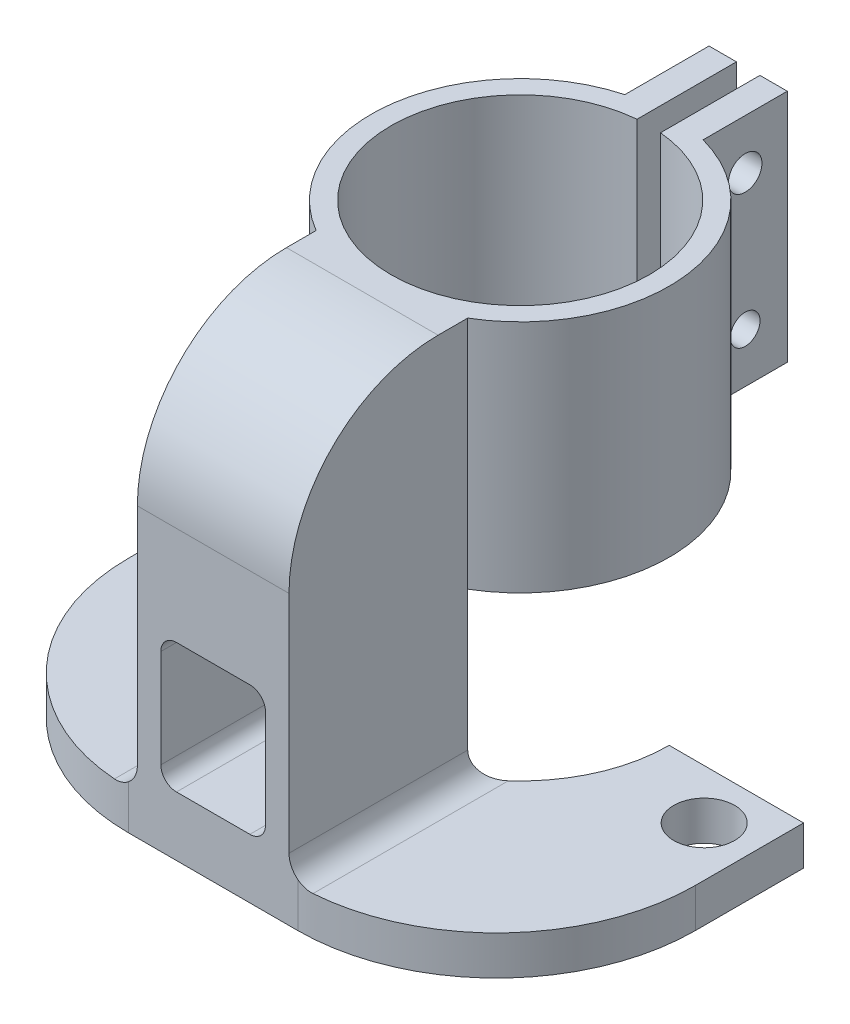
SolidWorks part; units mm, degrees
ref_plane "Front Plane" through (0, 0, 0) normal (0, 0, 1) x (1, 0, 0)
ref_plane "Top Plane" through (0, 0, 0) normal (0, 1, 0) x (1, 0, 0)
ref_plane "Right Plane" through (0, 0, 0) normal (1, 0, 0) x (0, 0, -1)
sketch "Sketch1" plane through (0, 0, 0) normal (0, 1, 0) x (1, 0, 0)
  line L0 (-5, 18.3718) -> (-5, 29.1317)
  line L3 (-5, 29.1317) -> (-1.5, 29.1317)
  line L5 (1.5, 29.1317) -> (5, 29.1317)
  line L7 (5, 18.3718) -> (5, 29.1317)
  line L8 (-1.5, 29.1317) -> (-1.5, 16.4317)
  line L10 (1.5, 29.1317) -> (1.5, 16.4317)
  arc A0 (-1.5, 16.4317) -> (1.5, 16.4317) centre (0, 0) ccw
  arc A1 (-5, 18.3718) -> (5, 18.3718) centre (0, 0) ccw
  circle A2 centre (0, 0) radius 19.04 construction
  circle A3 centre (0, 0) radius 16.5 construction
  dimension "D1" = 33
  dimension "D3" = 10
  dimension "D4" = 3
  dimension "D5" = 3.5
  dimension "D6" = 12.7
  dimension "D2" = 2.54
extrude "Clamp" add sketch "Sketch1" along normal blind 30
sketch "Sketch2" plane through (0, 30, 0) normal (0, 1, 0) x (1, 0, 0)
  line L0 (-9.687, -16.3916) -> (-9.687, -39.2263)
  line L3 (-9.687, -39.2263) -> (9.687, -39.2263)
  line L5 (0, -39.2263) -> (0, 0) construction
  line L9 (9.687, -16.3916) -> (9.687, -39.2263)
  arc A0 (-5, 18.3718) -> (5, 18.3718) centre (0, 0) ccw construction
  arc A1 (-5, 18.3718) -> (5, 18.3718) centre (0, 0) ccw
  point P0 (0, 0)
  arc M5 (-5, 18.3718) -> (5, 18.3718) centre (0, 0) ccw
extrude "Tower" add sketch "Sketch2" against normal blind 50.8 contours L5 L3 L9 A1 | L3 L5 L0 M5 region at (-4.9435, 30, 28.6903) region at (4.9435, 30, 28.6903)
sketch "Sketch3" plane through (0, -20.8, 0) normal (0, -1, 0) x (1, 0, 0)
  line L0 (-36.2099, 39.2263) -> (36.2099, 39.2263)
  line L1 (36.2099, 39.2263) -> (36.2099, 0)
  line L2 (36.2099, 0) -> (19.04, 0)
  line L3 (-36.2099, 0) -> (-36.2099, 39.2263)
  line L4 (0, 39.2263) -> (0, 0) construction
  line L5 (-29.8599, 6.35) -> (29.8599, 6.35) construction
  line L6 (-19.04, 0) -> (-36.2099, 0)
  circle A0 centre (-29.8599, 6.35) radius 4.0498
  circle A1 centre (29.8599, 6.35) radius 3.8918
  arc A2 (5, -18.3718) -> (9.687, 16.3916) centre (0, 0) ccw construction
  arc A3 (9.687, 16.3916) -> (-9.687, 16.3916) centre (0, 0) ccw construction
  arc A4 (-9.687, 16.3916) -> (-5, -18.3718) centre (0, 0) ccw construction
  arc A5 (19.04, 0) -> (9.687, 16.3916) centre (0, 0) ccw
  arc A6 (9.687, 16.3916) -> (-9.687, 16.3916) centre (0, 0) ccw
  arc A7 (-9.687, 16.3916) -> (-19.04, 0) centre (0, 0) ccw
  dimension "D1" = 6.35
  dimension "D2" = 6.35
  dimension "D3" = 6.35
extrude "Base" add sketch "Sketch3" along normal blind 5
fillet "Fillet1" radius 25.4 2 edges at (36.2099, -23.3, 39.2263) (-36.2099, -23.3, 39.2263)
fillet "Fillet2" radius 19.05 1 edges at (0, 30, 39.2263)
fillet "Fillet3" radius 3 2 edges at (9.687, -20.8, 27.809) (-9.687, -20.8, 27.809)
sketch "Sketch4" plane through (-5, 0, 0) normal (-1, 0, 0) x (0, 0, 1)
  line L0 (-23.7517, 30) -> (-23.7517, 0) construction
  line L1 (-29.1317, 30) -> (-18.3718, 30) construction
  line L2 (-29.1317, 0) -> (-18.3718, 0) construction
  circle A0 centre (-23.7517, 23.65) radius 2.141
  circle A1 centre (-23.7517, 6.35) radius 1.8937
  point P10 (0, 0)
  point P11 (0, 0)
  dimension "D1" = 6.35
  dimension "D2" = 6.35
extrude "Clamp Holes" cut sketch "Sketch4" against normal through all both and the other way through all
sketch "Sketch5" plane through (0, 0, 39.2263) normal (0, 0, 1) x (1, 0, 0)
  line L0 (-9.687, -17.8) -> (-9.687, 10.95) construction
  line L1 (-4.687, -18.2071) -> (4.687, -18.2071)
  line L2 (-6.687, -16.2071) -> (-6.687, -3.6633)
  line L3 (-4.687, -1.6633) -> (4.687, -1.6633)
  line L4 (6.687, -16.2071) -> (6.687, -3.6633)
  line L5 (9.687, -17.8) -> (9.687, 10.95) construction
  arc A0 (-4.687, -18.2071) -> (-6.687, -16.2071) centre (-4.687, -16.2071) cw
  arc A1 (4.687, -18.2071) -> (6.687, -16.2071) centre (4.687, -16.2071) ccw
  arc A2 (4.687, -1.6633) -> (6.687, -3.6633) centre (4.687, -3.6633) cw
  arc A3 (-6.687, -3.6633) -> (-4.687, -1.6633) centre (-4.687, -3.6633) cw
  dimension "D3" = 2
  dimension "D1" = 3
  dimension "D2" = 3
extrude "Motor Wire Cutout" cut sketch "Sketch5" against normal through all
equation "\"D2@Sketch5\"=\"D1@Sketch5\""
